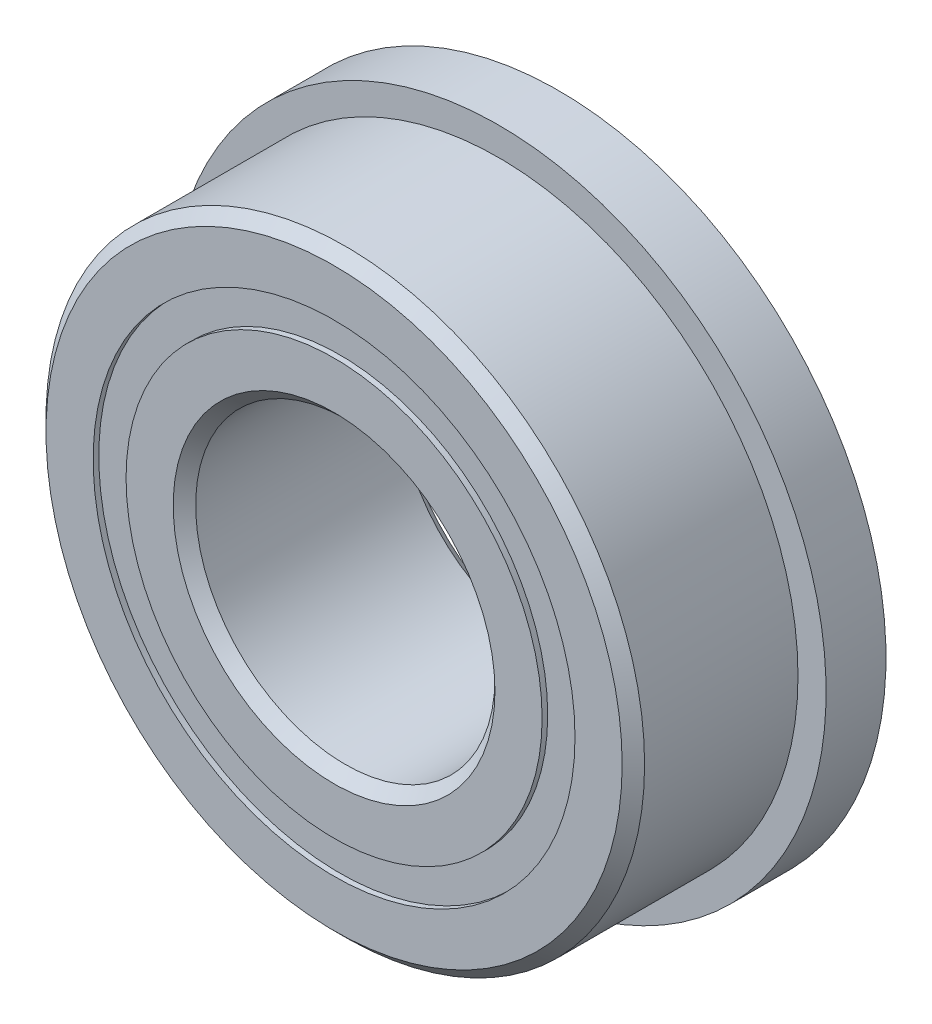
SolidWorks part; units mm, degrees
ref_plane "Front Plane" through (0, 0, 0) normal (0, 0, 1) x (1, 0, 0)
ref_plane "Top Plane" through (0, 0, 0) normal (0, 1, 0) x (1, 0, 0)
ref_plane "Right Plane" through (0, 0, 0) normal (1, 0, 0) x (0, 0, -1)
sketch "Sketch1" plane through (0, 0, 0) normal (1, 0, 0) x (0, 0, -1)
  line L0 (-2.3813, 0) -> (2.3813, 0) construction
  line L1 (0, 6.35) -> (0, -6.35) construction
  line L2 (2.3813, 6.35) -> (-2.3813, 6.35) construction
  line L9 (0, 6.35) -> (0, 4.7625) construction
  line L10 (0, 4.7625) -> (0, 3.175) construction
  point P14 (0, 3.175)
  dimension "Width" = 4.7625
  dimension "OD" = 12.7
  dimension "Shaft Dia" = 6.35
sketch "Sketch2" plane through (0, 0, 0) normal (1, 0, 0) x (0, 0, -1)
  line L0 (1.9844, 0) -> (-1.9844, 0) construction
  line L1 (2.3813, 5.1114) -> (1.1113, 5.1114) construction
  line L2 (2.3813, 5.1114) -> (2.3813, 6.9469) construction
  line L3 (2.3813, 6.9469) -> (1.1113, 6.9469) construction
  line L4 (1.1113, 5.1114) -> (1.1113, 6.9469) construction
  dimension "Th" = 1.27
  dimension "Flange OD" = 13.8938
  dimension "D1" = 0.3489
sketch "Sketch" plane through (0, 0, 0) normal (1, 0, 0) x (0, 0, -1)
  line L0 (-2.3812, 0) -> (2.3812, 0) construction
  line L1 (0, 6.35) -> (0, -6.35) construction
  line L2 (2.1431, 6.35) -> (-2.1431, 6.35)
  line L3 (-2.1431, 6.35) -> (-2.3813, 6.1119)
  line L4 (-2.3813, 6.1119) -> (-2.3813, 5.1114)
  line L5 (-2.3813, 5.1114) -> (-1.0583, 5.1114)
  line L6 (2.3813, 5.1114) -> (1.0583, 5.1114)
  line L7 (2.3813, 6.1119) -> (2.3813, 5.1114)
  line L8 (2.1431, 6.35) -> (2.3813, 6.1119)
  line L9 (0, 6.35) -> (0, 4.7625) construction
  line L10 (0, 4.7625) -> (0, 3.175) construction
  arc A0 (-1.0583, 5.1114) -> (1.0583, 5.1114) centre (0, 4.7625) cw
  point P14 (0, 3.175)
  dimension "D1" = 45
  dimension "D2" = 0.2381
  dimension "D3" = 2.1167
  dimension "D4" = 0.3489
revolve "Revolve1" add sketch "Sketch" angle 360 about L0
sketch "Sketch3" plane through (0, 0, 0) normal (1, 0, 0) x (0, 0, -1)
  line L0 (-2.3813, 4.4136) -> (-1.0583, 4.4136)
  line L1 (0, 6.35) -> (0, -6.35) construction
  line L2 (-2.3813, 6.1119) -> (-2.3813, 5.1114) construction
  line L3 (-2.3813, 4.4136) -> (-2.3813, 3.4131)
  line L4 (-2.1431, 6.35) -> (-2.3813, 6.1119) construction
  line L5 (-2.3813, 3.4131) -> (-2.1431, 3.175)
  line L6 (-2.1431, 3.175) -> (2.1431, 3.175)
  line L7 (2.1431, 6.35) -> (2.1431, -6.35) construction
  line L8 (2.1431, 3.175) -> (2.3812, 3.4131)
  line L9 (2.3813, -6.1119) -> (2.3813, 6.1119) construction
  line L10 (2.3812, 3.4131) -> (2.3813, 4.4136)
  line L11 (2.3813, 4.4136) -> (1.0583, 4.4136)
  line L13 (2.1431, 6.35) -> (2.3813, 6.1119) construction
  arc A0 (1.0583, 5.1114) -> (-1.0583, 5.1114) centre (0, 4.7625) ccw construction
  arc A1 (1.0583, 4.4136) -> (-1.0583, 4.4136) centre (0, 4.7625) cw
revolve "Revolve3" add sketch "Sketch3" angle 360 about L0
sketch "Sketch4" plane through (0, 0, 0) normal (1, 0, 0) x (0, 0, -1)
  line L0 (-1.1144, 4.7625) -> (1.1144, 4.7625)
  arc A2 (-1.1144, 4.7625) -> (1.1144, 4.7625) centre (0, 4.7625) cw
  arc A3 (1.0583, 5.1114) -> (-1.0583, 5.1114) centre (0, 4.7625) ccw construction
revolve "Revolve4" add sketch "Sketch4" angle 360 about L0
ref_axis "Axis1" through (0, 0, -2.3812) along (0, 0, 1)
pattern_circular "CirPattern1" count 12 every 30 about axis through (0, 0, -2.3812) along (0, 0, 1) of bodies 104
sketch "Sketch5" plane through (0, 0, 0) normal (1, 0, 0) x (0, 0, -1)
  line L0 (-2.3813, 5.1114) -> (-1.0583, 5.1114) construction
  line L1 (-2.2622, 5.1114) -> (-1.1144, 5.1114)
  line L2 (-2.2622, 5.1114) -> (-2.2622, 4.4136)
  line L3 (-2.2622, 4.4136) -> (-1.1144, 4.4136)
  line L4 (-1.1144, 5.1114) -> (-1.1144, 4.4136)
  line L5 (-2.3813, 4.4136) -> (-1.0583, 4.4136) construction
  line L6 (2.3813, 5.1114) -> (1.0583, 5.1114) construction
  line L7 (2.2622, 5.1114) -> (1.1144, 5.1114)
  line L8 (2.2622, 5.1114) -> (2.2622, 4.4136)
  line L9 (2.2622, 4.4136) -> (1.1144, 4.4136)
  line L10 (1.1144, 5.1114) -> (1.1144, 4.4136)
  line L11 (2.3813, 4.4136) -> (1.0583, 4.4136) construction
  line L12 (-2.1431, 6.35) -> (-2.3813, 6.1119) construction
  point P18 (-2.2622, 6.2309)
revolve "Revolve5" add sketch "Sketch5" angle 360 about L0
sketch "Sketch6" plane through (0, 0, 0) normal (1, 0, 0) x (0, 0, -1)
  line L0 (2.3812, 0) -> (-2.3812, 0) construction
  line L1 (2.3813, 5.1114) -> (1.1112, 5.1114)
  line L2 (2.3813, 5.1114) -> (2.3812, 6.9469)
  line L3 (2.3812, 6.9469) -> (1.1112, 6.9469)
  line L4 (1.1112, 5.1114) -> (1.1112, 6.9469)
  dimension "Th" = 1.27
  dimension "Flange OD" = 13.8938
revolve "Revolve6" add sketch "Sketch6" angle 360 about L0
sketch "Sketch7" plane through (0, 0, 0) normal (1, 0, 0) x (0, 0, -1)
  line L1 (2.3813, 6.35) -> (-2.3813, 6.35) construction
  line L2 (2.3813, 6.35) -> (-2.3813, 6.35) construction
  line L3 (2.3812, -6.35) -> (-2.3813, -6.35) construction
  line L4 (2.3812, -6.9469) -> (2.3812, 6.9469) construction
  line L5 (2.3813, 6.35) -> (2.3812, 6.9469) construction
  line L6 (2.3812, 6.9469) -> (1.1112, 6.9469) construction
  dimension "D1" = 12.7
  dimension "D2" = 4.7625
sketch "Sketch8" plane through (0, 0, 0) normal (0, 0, 1) x (1, 0, 0)
  circle A0 centre (0, 0) radius 3.175 construction
  dimension "D1" = 6.35
equation "\"D2@Sketch\" = \"Width@Sketch1\" * .05"
equation "\"D3@Sketch\" = \"Width@Sketch1\" / 2.25"
equation "\"D4@Sketch\"=(  (  ( \"OD@Sketch1\" - \"Width@Sketch1\" )  / 2 )  / 3.25 )  / 3.5"
equation "\"D2@CirPattern1\" = 360/\"Balls@CirPattern1\""
equation "\"D1@Sketch2\"=(  (  ( \"OD@Sketch1\" - \"Width@Sketch1\" )  / 2 )  / 3.25 )  / 3.5"
